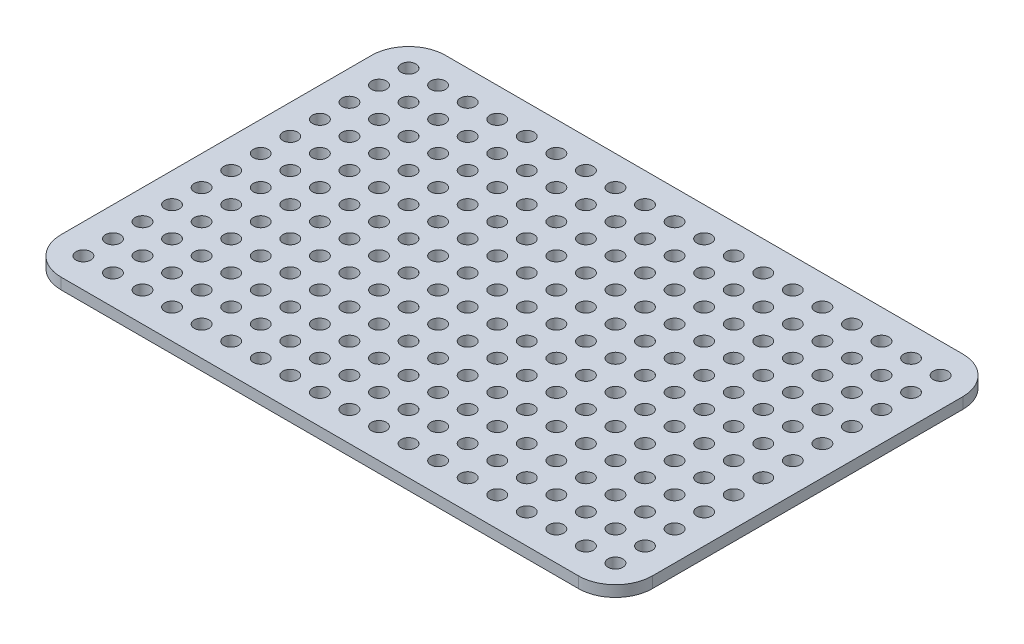
SolidWorks part; units mm, degrees
ref_plane "Front Plane" through (0, 0, 0) normal (0, 0, 1) x (1, 0, 0)
ref_plane "Top Plane" through (0, 0, 0) normal (0, 1, 0) x (1, 0, 0)
ref_plane "Right Plane" through (0, 0, 0) normal (1, 0, 0) x (0, 0, -1)
sketch "Sketch1" plane through (0, 0, 0) normal (0, 1, 0) x (1, 0, 0)
  line L1 (0, 0) -> (160, 0)
  line L2 (0, 0) -> (0, 104)
  line L3 (0, 104) -> (160, 104)
  line L4 (160, 0) -> (160, 104)
  dimension "D1" = 160
  dimension "D2" = 104
extrude "Boss-Extrude1" add sketch "Sketch1" along normal blind 3
fillet "Fillet1" radius 10 4 edges at (160, 1.5, 0) (160, 1.5, -104) (0, 1.5, 0) (0, 1.5, -104)
sketch "Sketch2" plane through (0, 3, 0) normal (0, 1, 0) x (1, 0, 0)
  line L0 (150, 104) -> (10, 104) construction
  line L1 (0, 94) -> (0, 10) construction
  circle A0 centre (8, 96) radius 2
  dimension "D1" = 4
  dimension "D2" = 8
  dimension "D3" = 8
extrude "Cut-Extrude1" cut sketch "Sketch2" against normal blind 3
pattern_linear "LPattern1" count 19 spacing 8 along (1, 0, 0) count 12 spacing 8 along (0, 0, 1) of "Cut-Extrude1"
equation "\"length\" = 160mm"
equation "\"width\" = 104mm"
equation "\"hole_diam\"= 4mm"
equation "\"hole_spacing\"= \"hole_diam\" * 2"
equation "\"wall_thickness\"= 3mm"
equation "\"D1@Sketch1\"=\"length\""
equation "\"D2@Sketch1\"=\"width\""
equation "\"fillet_radius\"= 10mm"
equation "\"D1@Boss-Extrude1\"=\"wall_thickness\""
equation "\"D1@Sketch2\"= \"hole_diam\""
equation "\"D2@Sketch2\"=\"hole_spacing\""
equation "\"D3@Sketch2\"=\"hole_spacing\""
equation "\"D1@Cut-Extrude1\"= \"wall_thickness\""
equation "\"D3@LPattern1\"= \"hole_spacing\""
equation "\"D4@LPattern1\"=\"hole_spacing\""
equation "\"D1@LPattern1\" = int ( \"length\" / \"hole_spacing\" ) - 1"
equation "\"D2@LPattern1\" = int ( \"width\" / \"hole_spacing\" ) - 1"
